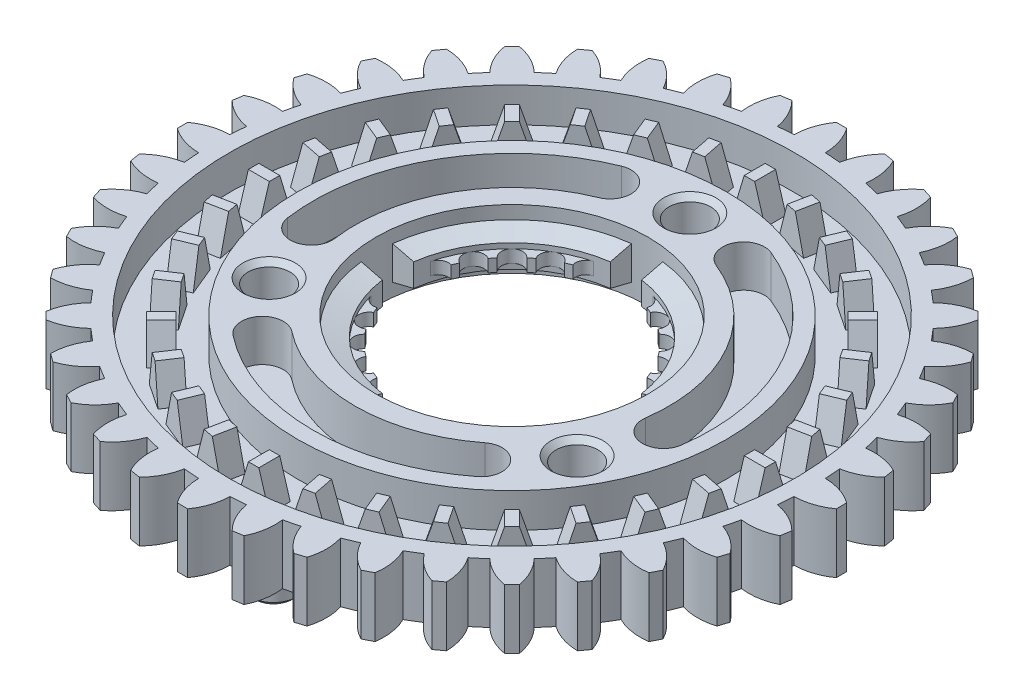
SolidWorks part; units mm, degrees
ref_plane "前视基准面" through (0, 0, 0) normal (0, 0, 1) x (1, 0, 0)
ref_plane "上视基准面" through (0, 0, 0) normal (0, 1, 0) x (1, 0, 0)
ref_plane "右视基准面" through (0, 0, 0) normal (1, 0, 0) x (0, 0, -1)
sketch "草图1" plane through (0, 0, 0) normal (0, 1, 0) x (1, 0, 0)
  circle A0 centre (0, 0) radius 28.5
  dimension "D1" = 57
extrude "凸台-拉伸1" add sketch "草图1" along normal blind 5.7
sketch "草图2" plane through (0, 0, 0) normal (0, 1, 0) x (1, 0, 0)
  line L0 (0, 0) -> (0, 28.5) construction
  line L1 (0, 28.5) -> (0, 31.5) construction
  line L2 (0.5, 31.5) -> (-0.5, 31.5)
  line L3 (0, 30) -> (-1.25, 30) construction
  line L4 (0, 28.5) -> (-1.5, 28.5) construction
  circle A0 centre (0, 0) radius 28.5 construction
  arc A1 (-0.5, 31.5) -> (-1.5008, 28.4605) centre (3.875, 28.375) ccw
  arc A2 (1.5008, 28.4605) -> (-1.5008, 28.4605) centre (0, 0) ccw
  arc A3 (0.5, 31.5) -> (1.5008, 28.4605) centre (-3.875, 28.375) cw
  dimension "D5" = 57
  dimension "D1" = 0.5
  dimension "D2" = 3
  dimension "D3" = 1.25
  dimension "D4" = 1.5
extrude "凸台-拉伸2" add sketch "草图2" along normal blind 5.7
pattern_circular "阵列(圆周)1" count 40 over 360 about axis through (0, 0, 0) along (0, 1, 0) of "凸台-拉伸2"
sketch "草图3" plane through (0, 5.7, 0) normal (0, 1, 0) x (1, 0, 0)
  circle A0 centre (0, 0) radius 27
  circle A1 centre (0, 0) radius 20.5
  dimension "D1" = 54
  dimension "D2" = 41
extrude "切除-拉伸1" cut sketch "草图3" against normal blind 3.3
sketch "草图4" plane through (0, 2.4, 0) normal (0, 1, 0) x (1, 0, 0)
  line L0 (0, 0) -> (0, 20.5) construction
  line L1 (0, 20.5) -> (0, 22.7) construction
  line L2 (0, 22.7) -> (0, 24.7) construction
  line L3 (1.5, 24.7) -> (-1.5, 24.7)
  line L4 (-1.5, 24.7) -> (-1.5, 22.7)
  line L5 (-1.5, 22.7) -> (1.5, 22.7)
  line L6 (1.5, 24.7) -> (1.5, 22.7)
  circle A0 centre (0, 0) radius 20.5 construction
  circle A1 centre (0, 0) radius 20.5 construction
  dimension "D1" = 2.2
  dimension "D2" = 2
  dimension "D3" = 1.5
sketch "草图5" plane through (0, 5.7, 0) normal (0, 1, 0) x (1, 0, 0)
  line L0 (0, 20.5) -> (0, 22.7) construction
  line L1 (0, 22.7) -> (0, 24.7) construction
  line L2 (0.5, 24.7) -> (-0.5, 24.7)
  line L3 (1.5, 24.7) -> (-1.5, 24.7) construction
  line L4 (-0.5, 24.7) -> (-0.5, 22.7)
  line L5 (-1.5, 22.7) -> (1.5, 22.7) construction
  line L6 (-0.5, 22.7) -> (0.5, 22.7)
  line L7 (0.5, 24.7) -> (0.5, 22.7)
  dimension "D1" = 0.5
loft "放样1" add profiles "草图5", "草图4"
pattern_circular "阵列(圆周)2" count 32 over 360 about axis through (0, 0, 0) along (0, 1, 0) of "放样1"
sketch "草图6" plane through (0, 5.7, 0) normal (0, 1, 0) x (1, 0, 0)
  circle A0 centre (0, 0) radius 13
  dimension "D1" = 26
extrude "切除-拉伸2" cut sketch "草图6" against normal blind 1.25
sketch "草图8" plane through (0, 0, 0) normal (0, -1, 0) x (1, 0, 0)
  circle A0 centre (0, 0) radius 13
  dimension "D1" = 26
extrude "切除-拉伸3" cut sketch "草图8" against normal blind 1.25
sketch "草图9" plane through (0, 0, 0) normal (1, 0, 0) x (0, 0, -1)
  line L0 (0, 0) -> (0, 1.25) construction
  line L1 (0, 1.25) -> (13, 1.25)
  line L2 (0, 0) -> (0, 2.85) construction
  line L3 (0, 1.25) -> (0, 1.75)
  line L4 (0, 1.75) -> (11, 1.75)
  line L5 (11, 1.75) -> (13, 1.25)
  line L6 (0, 2.85) -> (4.0673, 2.85) construction
  line L7 (11, 3.95) -> (13, 4.45)
  line L8 (0, 4.45) -> (13, 4.45)
  line L9 (0, 4.45) -> (0, 3.95)
  line L10 (0, 3.95) -> (11, 3.95)
  dimension "D1" = 1.25
  dimension "D2" = 2.85
  dimension "D3" = 0.5
  dimension "D4" = 13
  dimension "D5" = 11
revolve "切除-旋转1" cut sketch "草图9" angle 360 about L2
sketch "草图10" plane through (0, 3.95, 0) normal (0, 1, 0) x (1, 0, 0)
  circle A0 centre (0, 0) radius 11
  dimension "D1" = 22
extrude "切除-拉伸4" cut sketch "草图10" against normal blind 0.5
sketch "草图11" plane through (0, 1.75, 0) normal (0, -1, 0) x (1, 0, 0)
  circle A0 centre (0, 0) radius 11
  dimension "D1" = 22
extrude "切除-拉伸5" cut sketch "草图11" against normal blind 0.5
sketch "草图12" plane through (0, 3.45, 0) normal (0, 1, 0) x (1, 0, 0)
  line L0 (0, 0) -> (0, 10) construction
  arc A0 (-3.54, 9.3525) -> (-4.1101, 9.1163) centre (0, 0) ccw
  arc A1 (0.9987, 9.95) -> (-0.9987, 9.95) centre (0, 10) ccw construction
  arc A2 (3.54, 9.3525) -> (2.847, 10.6252) centre (2.5882, 9.6593) ccw
  arc A3 (5.8399, 8.1176) -> (4.1101, 9.1163) centre (5, 8.6603) ccw
  arc A4 (7.7419, 6.3295) -> (6.3295, 7.7419) centre (7.0711, 7.0711) ccw
  arc A5 (9.1163, 4.1101) -> (8.1176, 5.8399) centre (8.6603, 5) ccw
  arc A6 (10.6252, 2.847) -> (9.3525, 3.54) centre (9.6593, 2.5882) ccw
  arc A7 (4.1101, 9.1163) -> (3.54, 9.3525) centre (0, 0) ccw
  arc A8 (9.3525, -3.54) -> (10.6252, -2.847) centre (9.6593, -2.5882) ccw
  arc A9 (8.1176, -5.8399) -> (9.1163, -4.1101) centre (8.6603, -5) ccw
  arc A10 (6.3295, -7.7419) -> (7.7419, -6.3295) centre (7.0711, -7.0711) ccw
  arc A11 (4.1101, -9.1163) -> (5.8399, -8.1176) centre (5, -8.6603) ccw
  arc A12 (2.847, -10.6252) -> (3.54, -9.3525) centre (2.5882, -9.6593) ccw
  arc A13 (5.8399, -8.1176) -> (6.3295, -7.7419) centre (0, 0) ccw
  arc A14 (-3.54, -9.3525) -> (-2.847, -10.6252) centre (-2.5882, -9.6593) ccw
  arc A15 (-5.8399, -8.1176) -> (-4.1101, -9.1163) centre (-5, -8.6603) ccw
  arc A16 (-7.7419, -6.3295) -> (-6.3295, -7.7419) centre (-7.0711, -7.0711) ccw
  arc A17 (-9.1163, -4.1101) -> (-8.1176, -5.8399) centre (-8.6603, -5) ccw
  arc A18 (-10.6252, -2.847) -> (-9.3525, -3.54) centre (-9.6593, -2.5882) ccw
  arc A19 (-2.847, -10.6252) -> (2.847, -10.6252) centre (0, 0) ccw
  arc A20 (-9.3525, 3.54) -> (-10.6252, 2.847) centre (-9.6593, 2.5882) ccw
  arc A21 (-8.1176, 5.8399) -> (-9.1163, 4.1101) centre (-8.6603, 5) ccw
  arc A22 (-6.3295, 7.7419) -> (-7.7419, 6.3295) centre (-7.0711, 7.0711) ccw
  arc A23 (-4.1101, 9.1163) -> (-5.8399, 8.1176) centre (-5, 8.6603) ccw
  arc A24 (-2.847, 10.6252) -> (-3.54, 9.3525) centre (-2.5882, 9.6593) ccw
  arc A25 (-10.6252, 2.847) -> (-10.6252, -2.847) centre (0, 0) ccw
  arc A26 (-5.8399, 8.1176) -> (-6.3295, 7.7419) centre (0, 0) ccw
  arc A27 (-7.7419, 6.3295) -> (-8.1176, 5.8399) centre (0, 0) ccw
  arc A28 (-9.1163, 4.1101) -> (-9.3525, 3.54) centre (0, 0) ccw
  arc A29 (-9.3525, -3.54) -> (-9.1163, -4.1101) centre (0, 0) ccw
  arc A30 (-11, 0) -> (-9.95, -0.9987) centre (-10, 0) ccw [skipped]
  arc A31 (-8.1176, -5.8399) -> (-7.7419, -6.3295) centre (0, 0) ccw
  arc A32 (-6.3295, -7.7419) -> (-5.8399, -8.1176) centre (0, 0) ccw
  arc A33 (-4.1101, -9.1163) -> (-3.54, -9.3525) centre (0, 0) ccw
  arc A34 (3.54, -9.3525) -> (4.1101, -9.1163) centre (0, 0) ccw
  arc A35 (0, -11) -> (0.9987, -9.95) centre (0, -10) ccw [skipped]
  arc A36 (7.7419, -6.3295) -> (8.1176, -5.8399) centre (0, 0) ccw
  arc A37 (9.1163, -4.1101) -> (9.3525, -3.54) centre (0, 0) ccw
  arc A38 (10.6252, -2.847) -> (10.6252, 2.847) centre (0, 0) ccw
  arc A39 (9.3525, 3.54) -> (9.1163, 4.1101) centre (0, 0) ccw
  arc A40 (11, 0) -> (9.95, 0.9987) centre (10, 0) ccw [skipped]
  arc A41 (6.3295, 7.7419) -> (5.8399, 8.1176) centre (0, 0) ccw
  arc A42 (8.1176, 5.8399) -> (7.7419, 6.3295) centre (0, 0) ccw
  arc A43 (2.847, 10.6252) -> (-2.847, 10.6252) centre (0, 0) ccw
  point P78 (0, 0)
  dimension "D1" = 20
  dimension "D2" = 1
  dimension "D4" = 22
  dimension "D3" = 24
extrude "切除-拉伸6" cut sketch "草图12" against normal through all
sketch "草图14" plane through (0, 5.7, 0) normal (0, 1, 0) x (1, 0, 0)
  line L1 (1.5, 10.8972) -> (1.5, 12.9132)
  line L3 (-1.5, 10.8972) -> (-1.5, 12.9132)
  arc A0 (1.5, 12.9132) -> (-1.5, 12.9132) centre (0, 0) ccw
  arc A1 (1.5, 10.8972) -> (-1.5, 10.8972) centre (0, 0) ccw
  dimension "D1" = 26
  dimension "D2" = 22
extrude "切除-拉伸7" cut sketch "草图14" against normal through all
pattern_circular "阵列(圆周)3" count 4 over 360 about axis through (0, 0, 0) along (0, 1, 0) of "切除-拉伸7"
sketch "草图15" plane through (0, 5.7, 0) normal (0, 1, 0) x (1, 0, 0)
  line L0 (0, 0) -> (0, 13) construction
  line L1 (0, 13) -> (0, 15) construction
  line L2 (0, 15) -> (0, 17) construction
  circle A0 centre (0, 0) radius 13 construction
  circle A1 centre (0, 17) radius 2
  dimension "D1" = 2
  dimension "D2" = 2
extrude "切除-拉伸8" cut sketch "草图15" against normal through all
chamfer "倒角1" distance 0.5 angle 45 2 edges at (0, 0, -15) (0, 5.7, -15)
pattern_circular "阵列(圆周)4" count 3 over 360 about axis through (0, 0, 0) along (0, 1, 0) of "切除-拉伸8", "倒角1"
sketch "草图16" plane through (0, 5.7, 0) normal (0, 1, 0) x (1, 0, 0)
  line L0 (0, 0) -> (0, 17) construction
  line L1 (0, 0) -> (-6.3801, 15.7574) construction
  line L2 (0, 0) -> (-14.7224, -8.5) construction
  line L3 (0, 0) -> (-16.8363, -2.3533) construction
  arc A0 (-5.6295, 13.9035) -> (-14.8556, -2.0765) centre (0, 0) ccw
  arc A1 (-7.1307, 17.6112) -> (-18.8171, -2.6302) centre (0, 0) ccw
  circle A2 centre (0, 0) radius 17 construction
  arc A3 (-5.6295, 13.9035) -> (-7.1307, 17.6112) centre (-6.3801, 15.7574) ccw
  arc A4 (-18.8171, -2.6302) -> (-14.8556, -2.0765) centre (-16.8363, -2.3533) ccw
  dimension "D2" = 38
  dimension "D3" = 34
  dimension "D4" = 6.5
  dimension "D5" = 6.5
extrude "切除-拉伸9" cut sketch "草图16" against normal blind 4
pattern_circular "阵列(圆周)5" count 3 over 360 about axis through (0, 0, 0) along (0, 1, 0) of "切除-拉伸9"
sketch "草图17" plane through (0, 0, 0) normal (0, -1, 0) x (1, 0, 0)
  line L0 (0, 0) -> (0, -17) construction
  line L1 (0, 0) -> (19.7454, -11.4) construction
  circle A0 centre (0, 0) radius 22.8 construction
  circle A1 centre (19.7454, -11.4) radius 2.2
  dimension "D1" = 45.6
  dimension "D3" = 4.4
  dimension "D2" = 60
extrude "凸台-拉伸3" add sketch "草图17" along normal blind 5.5
chamfer "倒角2" distance 0.4 angle 45 1 edges at (19.7454, -5.5, -13.6)
pattern_circular "阵列(圆周)6" count 3 over 360 about axis through (0, 0, 0) along (0, 1, 0) of "凸台-拉伸3", "倒角2"
